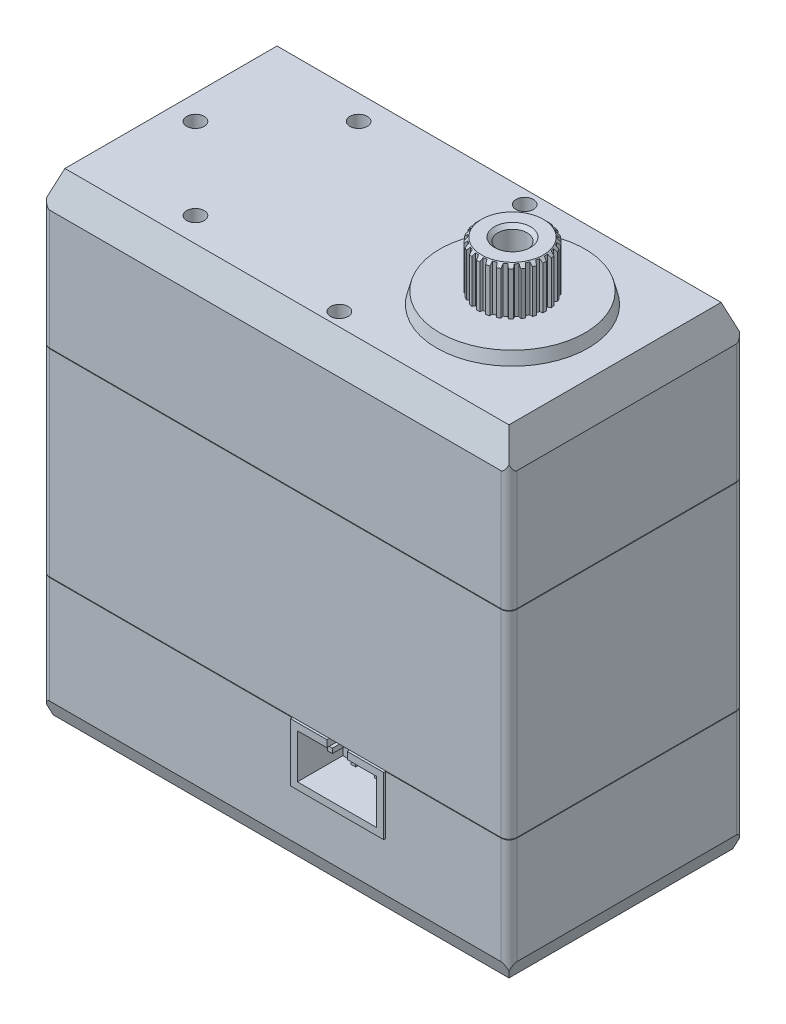
SolidWorks part; units mm, degrees
ref_plane "Front Plane" through (0, 0, 0) normal (0, 0, 1) x (1, 0, 0)
ref_plane "Top Plane" through (0, 0, 0) normal (0, 1, 0) x (1, 0, 0)
ref_plane "Right Plane" through (0, 0, 0) normal (1, 0, 0) x (0, 0, -1)
sketch "Sketch1" plane through (0, 0, 0) normal (0, 1, 0) x (1, 0, 0)
  line L1 (9.8, -10.1) -> (-30.3, -10.1)
  line L2 (9.8, -10.1) -> (9.8, 10.1)
  line L3 (9.8, 10.1) -> (-30.3, 10.1)
  line L4 (-30.3, -10.1) -> (-30.3, 10.1)
  line L5 (9.8, -10.1) -> (-30.3, 10.1) construction
  line L6 (9.8, 10.1) -> (-30.3, -10.1) construction
  point P0 (-10.25, 0)
  dimension "D1" = 20.2
  dimension "D2" = 40.1
  dimension "D3" = 9.8
extrude "Boss-Extrude1" add sketch "Sketch1" along normal blind 40.6
sketch "Sketch2" plane through (0, 0, 0) normal (0, -1, 0) x (1, 0, 0)
  circle A0 centre (0, 0) radius 6.5
  dimension "D1" = 13
extrude "Boss-Extrude2" add sketch "Sketch2" along normal blind 1.5 draft 15
extrude "Boss-Extrude3" add sketch "Sketch2<2>" against normal blind 1 draft 15 from surface starting at face at (-10.25, 40.6, 0)
sketch "Sketch2<2>" plane through (0, 0, 0) normal (0, -1, 0) x (1, 0, 0) same geometry as "Sketch2"
sketch "Sketch3" plane through (0, 41.6, 0) normal (0, 1, 0) x (1, 0, 0)
  circle A0 centre (0, 0) radius 2.95
  dimension "D1" = 5.9
extrude "Boss-Extrude4" add sketch "Sketch3" along normal blind 4
chamfer "Chamfer1" distance 0.3 angle 45 1 edges at (0, 45.6, 2.95)
sketch "Sketch4" plane through (0, 45.6, 0) normal (0, 1, 0) x (1, 0, 0)
  line L0 (-0.2268, 2.9413) -> (-0.144, 2.7138)
  line L1 (-0.144, 2.7138) -> (0.144, 2.7138)
  line L2 (0.144, 2.7138) -> (0.2268, 2.9413)
  line L3 (0, 0) -> (0, 2.95) construction
  line L4 (0.5118, 2.9053) -> (0.5354, 2.6643)
  line L5 (0.5354, 2.6643) -> (0.8144, 2.5927)
  line L6 (0.8144, 2.5927) -> (0.9512, 2.7925)
  line L7 (1.2182, 2.6867) -> (1.1812, 2.4475)
  line L8 (1.1812, 2.4475) -> (1.4336, 2.3087)
  line L9 (1.4336, 2.3087) -> (1.6157, 2.4682)
  line L10 (1.8481, 2.2994) -> (1.7527, 2.0769)
  line L11 (1.7527, 2.0769) -> (1.9627, 1.8797)
  line L12 (1.9627, 1.8797) -> (2.1788, 1.9888)
  line L13 (2.3619, 1.7675) -> (2.2142, 1.5757)
  line L14 (2.2142, 1.5757) -> (2.3685, 1.3325)
  line L15 (2.3685, 1.3325) -> (2.6049, 1.3845)
  line L16 (2.7272, 1.1246) -> (2.5365, 0.9756)
  line L17 (2.5365, 0.9756) -> (2.6255, 0.7016)
  line L18 (2.6255, 0.7016) -> (2.8674, 0.6932)
  line L19 (2.9212, 0.4111) -> (2.6994, 0.3141)
  line L20 (2.6994, 0.3141) -> (2.7175, 0.0267)
  line L21 (2.7175, 0.0267) -> (2.9497, -0.0417)
  line L22 (2.9317, -0.3283) -> (2.6927, -0.367)
  line L23 (2.6927, -0.367) -> (2.6387, -0.65)
  line L24 (2.6387, -0.65) -> (2.8467, -0.7739)
  line L25 (2.7579, -1.0471) -> (2.5168, -1.0252)
  line L26 (2.5168, -1.0252) -> (2.3942, -1.2858)
  line L27 (2.3942, -1.2858) -> (2.5648, -1.4576)
  line L28 (2.4109, -1.7001) -> (2.1828, -1.6189)
  line L29 (2.1828, -1.6189) -> (1.9992, -1.8408)
  line L30 (1.9992, -1.8408) -> (2.1217, -2.0496)
  line L31 (1.9123, -2.2462) -> (1.7116, -2.1108)
  line L32 (1.7116, -2.1108) -> (1.4786, -2.2802)
  line L33 (1.4786, -2.2802) -> (1.5453, -2.5129)
  line L34 (1.2936, -2.6512) -> (1.1329, -2.4702)
  line L35 (1.1329, -2.4702) -> (0.8651, -2.5762)
  line L36 (0.8651, -2.5762) -> (0.8719, -2.8182)
  line L37 (0.5937, -2.8896) -> (0.483, -2.6743)
  line L38 (0.483, -2.6743) -> (0.1972, -2.7104)
  line L39 (0.1972, -2.7104) -> (0.1436, -2.9465)
  line L40 (-0.1436, -2.9465) -> (-0.1972, -2.7104)
  line L41 (-0.1972, -2.7104) -> (-0.483, -2.6743)
  line L42 (-0.483, -2.6743) -> (-0.5937, -2.8896)
  line L43 (-0.8719, -2.8182) -> (-0.8651, -2.5762)
  line L44 (-0.8651, -2.5762) -> (-1.1329, -2.4702)
  line L45 (-1.1329, -2.4702) -> (-1.2936, -2.6512)
  line L46 (-1.5453, -2.5129) -> (-1.4786, -2.2802)
  line L47 (-1.4786, -2.2802) -> (-1.7116, -2.1108)
  line L48 (-1.7116, -2.1108) -> (-1.9123, -2.2462)
  line L49 (-2.1217, -2.0496) -> (-1.9992, -1.8408)
  line L50 (-1.9992, -1.8408) -> (-2.1828, -1.6189)
  line L51 (-2.1828, -1.6189) -> (-2.4109, -1.7001)
  line L52 (-2.5648, -1.4576) -> (-2.3942, -1.2858)
  line L53 (-2.3942, -1.2858) -> (-2.5168, -1.0252)
  line L54 (-2.5168, -1.0252) -> (-2.7579, -1.0471)
  line L55 (-2.8467, -0.7739) -> (-2.6387, -0.65)
  line L56 (-2.6387, -0.65) -> (-2.6927, -0.367)
  line L57 (-2.6927, -0.367) -> (-2.9317, -0.3283)
  line L58 (-2.9497, -0.0417) -> (-2.7175, 0.0267)
  line L59 (-2.7175, 0.0267) -> (-2.6994, 0.3141)
  line L60 (-2.6994, 0.3141) -> (-2.9212, 0.4111)
  line L61 (-2.8674, 0.6932) -> (-2.6255, 0.7016)
  line L62 (-2.6255, 0.7016) -> (-2.5365, 0.9756)
  line L63 (-2.5365, 0.9756) -> (-2.7272, 1.1246)
  line L64 (-2.6049, 1.3845) -> (-2.3685, 1.3325)
  line L65 (-2.3685, 1.3325) -> (-2.2142, 1.5757)
  line L66 (-2.2142, 1.5757) -> (-2.3619, 1.7675)
  line L67 (-2.1788, 1.9888) -> (-1.9627, 1.8797)
  line L68 (-1.9627, 1.8797) -> (-1.7527, 2.0769)
  line L69 (-1.7527, 2.0769) -> (-1.8481, 2.2994)
  line L70 (-1.6157, 2.4682) -> (-1.4336, 2.3087)
  line L71 (-1.4336, 2.3087) -> (-1.1812, 2.4475)
  line L72 (-1.1812, 2.4475) -> (-1.2182, 2.6867)
  line L73 (-0.9512, 2.7925) -> (-0.8144, 2.5927)
  line L74 (-0.8144, 2.5927) -> (-0.5354, 2.6643)
  line L75 (-0.5354, 2.6643) -> (-0.5118, 2.9053)
  circle A0 centre (0, 0) radius 2.95 construction
  arc A1 (0.2268, 2.9413) -> (-0.2268, 2.9413) centre (0, 0) ccw
  arc A2 (0.9512, 2.7925) -> (0.5118, 2.9053) centre (0, 0) ccw
  arc A3 (1.6157, 2.4682) -> (1.2182, 2.6867) centre (0, 0) ccw
  arc A4 (2.1788, 1.9888) -> (1.8481, 2.2994) centre (0, 0) ccw
  arc A5 (2.6049, 1.3845) -> (2.3619, 1.7675) centre (0, 0) ccw
  arc A6 (2.8674, 0.6932) -> (2.7272, 1.1246) centre (0, 0) ccw
  arc A7 (2.9497, -0.0417) -> (2.9212, 0.4111) centre (0, 0) ccw
  arc A8 (2.8467, -0.7739) -> (2.9317, -0.3283) centre (0, 0) ccw
  arc A9 (2.5648, -1.4576) -> (2.7579, -1.0471) centre (0, 0) ccw
  arc A10 (2.1217, -2.0496) -> (2.4109, -1.7001) centre (0, 0) ccw
  arc A11 (1.5453, -2.5129) -> (1.9123, -2.2462) centre (0, 0) ccw
  arc A12 (0.8719, -2.8182) -> (1.2936, -2.6512) centre (0, 0) ccw
  arc A13 (0.1436, -2.9465) -> (0.5937, -2.8896) centre (0, 0) ccw
  arc A14 (-0.5937, -2.8896) -> (-0.1436, -2.9465) centre (0, 0) ccw
  arc A15 (-1.2936, -2.6512) -> (-0.8719, -2.8182) centre (0, 0) ccw
  arc A16 (-1.9123, -2.2462) -> (-1.5453, -2.5129) centre (0, 0) ccw
  arc A17 (-2.4109, -1.7001) -> (-2.1217, -2.0496) centre (0, 0) ccw
  arc A18 (-2.7579, -1.0471) -> (-2.5648, -1.4576) centre (0, 0) ccw
  arc A19 (-2.9317, -0.3283) -> (-2.8467, -0.7739) centre (0, 0) ccw
  arc A20 (-2.9212, 0.4111) -> (-2.9497, -0.0417) centre (0, 0) ccw
  arc A21 (-2.7272, 1.1246) -> (-2.8674, 0.6932) centre (0, 0) ccw
  arc A22 (-2.3619, 1.7675) -> (-2.6049, 1.3845) centre (0, 0) ccw
  arc A23 (-1.8481, 2.2994) -> (-2.1788, 1.9888) centre (0, 0) ccw
  arc A24 (-1.2182, 2.6867) -> (-1.6157, 2.4682) centre (0, 0) ccw
  arc A25 (-0.5118, 2.9053) -> (-0.9512, 2.7925) centre (0, 0) ccw
  point P4 (0, 2.7138)
  point P106 (0, 0)
  dimension "D1" = 110
  dimension "D4" = 25
extrude "Cut-Extrude1" cut sketch "Sketch4" against normal up to surface (4 mm away) up to face at (0, 41.6, 2.95)
sketch "Sketch5" plane through (0, 45.6, 0) normal (0, 1, 0) x (1, 0, 0)
  circle A0 centre (0, 0) radius 1.25
  dimension "D1" = 2.5
extrude "Cut-Extrude2" cut sketch "Sketch5" against normal blind 5
chamfer "Chamfer2" distance 0.3 angle 45 1 edges at (0, 45.6, 1.25)
sketch "Sketch6" plane through (0, -1.5, 0) normal (0, -1, 0) x (1, 0, 0)
  circle A0 centre (0, 0) radius 3
  circle A1 centre (0, 0) radius 1.2
  dimension "D1" = 6
  dimension "D2" = 2.4
extrude "Boss-Extrude5" add sketch "Sketch6" along normal blind 4.4
chamfer "Chamfer3" distance 0.3 angle 45 1 edges at (0, -5.9, -3)
sketch "Sketch7" plane through (0, 40.6, 0) normal (0, 1, 0) x (1, 0, 0)
  line L0 (-20.2, 7) -> (-20.2, -7) construction
  line L1 (-6.9, 7.95) -> (-6.9, -7.95) construction
  line L2 (0, 0) -> (-27.2, 0) construction
  line L3 (-30.3, 10.1) -> (-30.3, -10.1) construction
  circle A0 centre (-20.2, 7) radius 0.75
  circle A1 centre (-6.9, 7.95) radius 0.75
  circle A2 centre (-6.9, -7.95) radius 0.75
  circle A3 centre (-20.2, -7) radius 0.75
  circle A4 centre (-27.2, 0) radius 0.75
  point P7 (-20.2, 0)
  point P8 (-6.9, 0)
  dimension "D6" = 1.5
  dimension "D1" = 14
  dimension "D2" = 15.9
  dimension "D3" = 7
  dimension "D4" = 3.1
  dimension "D5" = 13.3
extrude "Cut-Extrude3" cut sketch "Sketch7" against normal blind 5
sketch "Sketch8" plane through (0, 0, 0) normal (0, -1, 0) x (1, 0, 0)
  line L0 (9.8, -10.1) -> (-30.3, -10.1) construction
  line L1 (-27.85, 7.6) -> (7.35, 7.6) construction
  line L2 (-27.85, 7.6) -> (-27.85, -7.6) construction
  line L3 (-27.85, -7.6) -> (7.35, -7.6) construction
  line L4 (7.35, 7.6) -> (7.35, -7.6) construction
  line L5 (-30.3, -10.1) -> (-30.3, 10.1) construction
  line L6 (-12.75, 7.6) -> (-12.75, -7.6) construction
  circle A0 centre (-27.85, 7.6) radius 0.75
  circle A1 centre (-12.75, 7.6) radius 0.75
  circle A2 centre (7.35, 7.6) radius 0.75
  circle A3 centre (7.35, -7.6) radius 0.75
  circle A4 centre (-12.75, -7.6) radius 0.75
  circle A5 centre (-27.85, -7.6) radius 0.75
  point P6 (-10.25, -10.1)
  point P7 (-10.25, -7.6)
  point P10 (-30.3, 0)
  point P11 (-27.85, 0)
  dimension "D4" = 1.5
  dimension "D1" = 15.2
  dimension "D2" = 35.2
  dimension "D3" = 15.1
extrude "Cut-Extrude4" cut sketch "Sketch8" against normal blind 5
sketch "Sketch9" plane through (0, 40.6, 0) normal (0, 1, 0) x (1, 0, 0)
  line L0 (-30.25, 10.05) -> (-30.25, -10.05)
  line L1 (-30.25, -10.05) -> (9.75, -10.05)
  line L2 (9.75, -10.05) -> (9.75, 10.05)
  line L3 (9.75, 10.05) -> (-30.25, 10.05)
  line L4 (-30.3, 10.1) -> (-30.3, -10.1)
  line L5 (-30.3, -10.1) -> (9.8, -10.1)
  line L6 (9.8, -10.1) -> (9.8, 10.1)
  line L7 (9.8, 10.1) -> (-30.3, 10.1)
  line L8 (-30.3, 10.1) -> (-30.3, -10.1)
  line L9 (-30.3, -10.1) -> (9.8, -10.1)
  line L10 (9.8, -10.1) -> (9.8, 10.1)
  line L11 (9.8, 10.1) -> (-30.3, 10.1)
  dimension "D1" = 0
  dimension "D2" = 0.05
extrude "Cut-Extrude5" cut sketch "Sketch9" against normal blind 0.05 from offset 13 offset against normal yes
extrude "Cut-Extrude6" cut sketch "Sketch9<2>" against normal blind 0.05 from offset 30 offset against normal yes
sketch "Sketch9<2>" plane through (0, 40.6, 0) normal (0, 1, 0) x (1, 0, 0) same geometry as "Sketch9"
chamfer "Chamfer4" distance 1 angle 70 4 edges at (9.8, 40.6, 0) (-10.25, 40.6, -10.1) (-30.3, 40.6, 0) (-10.25, 40.6, 10.1) first distance on face at (-27.2, 40.6, 0.75)
chamfer "Chamfer5" distance 0.5 angle 70 4 edges at (-10.25, 0, 10.1) (9.8, 0, 0) (-10.25, 0, -10.1) (-30.3, 0, 0) first distance on face at (-27.85, 0, -8.35)
sketch "Sketch10" plane through (0, 0, 10.1) normal (0, 0, 1) x (1, 0, 0)
  line L0 (-30.3, 10.55) -> (9.8, 10.55) construction
  line L1 (-8.8, 10.55) -> (-0.8, 10.55)
  line L2 (-8.8, 10.55) -> (-8.8, 5.55)
  line L3 (-8.8, 5.55) -> (-0.8, 5.55)
  line L4 (-0.8, 10.55) -> (-0.8, 5.55)
  line L5 (-30.3, 10.55) -> (-30.3, 1.3737) construction
  line L6 (-8.2, 9.95) -> (-8.2, 6.15)
  line L7 (-8.2, 6.15) -> (-1.4, 6.15)
  line L8 (-1.4, 9.95) -> (-1.4, 6.15)
  line L9 (-8.2, 9.95) -> (-1.4, 9.95)
  dimension "D1" = 8
  dimension "D2" = 5
  dimension "D3" = 21.5
  dimension "D4" = 0.6
extrude "Boss-Extrude6" add sketch "Sketch10" along normal blind 0.15
sketch "Sketch11" plane through (0, 0, 10.1) normal (0, 0, 1) x (1, 0, 0)
  line L4 (-1.4, 6.15) -> (-1.4, 9.95)
  line L5 (-1.4, 9.95) -> (-8.2, 9.95)
  line L6 (-8.2, 9.95) -> (-8.2, 6.15)
  line L7 (-8.2, 6.15) -> (-1.4, 6.15)
  line L8 (-1.4, 6.15) -> (-1.4, 9.95)
  line L9 (-1.4, 9.95) -> (-8.2, 9.95)
  line L10 (-8.2, 9.95) -> (-8.2, 6.15)
  line L11 (-8.2, 6.15) -> (-1.4, 6.15)
  dimension "D1" = 0
extrude "Cut-Extrude7" cut sketch "Sketch11" against normal blind 3.75
sketch "Sketch12" plane through (0, 0, 10.25) normal (0, 0, 1) x (1, 0, 0)
  line L0 (-1.4, 9.95) -> (-8.2, 9.95) construction
  line L1 (-5.675, 9.95) -> (-3.925, 9.95)
  line L2 (-5.675, 9.95) -> (-5.675, 10.55)
  line L3 (-5.675, 10.55) -> (-3.925, 10.55)
  line L4 (-3.925, 9.95) -> (-3.925, 10.55)
  line L5 (-0.8, 10.55) -> (-8.8, 10.55) construction
  line L6 (-8.8, 5.55) -> (-0.8, 5.55) construction
  point P10 (-4.8, 5.55)
  point P11 (-4.8, 9.95)
  dimension "D1" = 1.75
extrude "Cut-Extrude8" cut sketch "Sketch12" against normal up to surface (3.9 mm away) up to face at (-4.8, 8.05, 6.35)
sketch "Sketch13" plane through (0, 0, 6.35) normal (0, 0, 1) x (1, 0, 0)
  line L0 (-6.8, 8.55) -> (-2.8, 8.55) construction
  line L1 (-8.2, 6.15) -> (-1.4, 6.15) construction
  line L2 (-6.6, 8.35) -> (-7, 8.35)
  line L3 (-6.6, 8.35) -> (-6.6, 8.75)
  line L4 (-6.6, 8.75) -> (-7, 8.75)
  line L5 (-7, 8.35) -> (-7, 8.75)
  line L6 (-6.6, 8.35) -> (-7, 8.75) construction
  line L7 (-6.6, 8.75) -> (-7, 8.35) construction
  line L8 (-4.6, 8.35) -> (-5, 8.35)
  line L9 (-4.6, 8.35) -> (-4.6, 8.75)
  line L10 (-4.6, 8.75) -> (-5, 8.75)
  line L11 (-5, 8.35) -> (-5, 8.75)
  line L12 (-4.6, 8.35) -> (-5, 8.75) construction
  line L13 (-4.6, 8.75) -> (-5, 8.35) construction
  line L14 (-2.6, 8.35) -> (-3, 8.35)
  line L15 (-2.6, 8.35) -> (-2.6, 8.75)
  line L16 (-2.6, 8.75) -> (-3, 8.75)
  line L17 (-3, 8.35) -> (-3, 8.75)
  line L18 (-2.6, 8.35) -> (-3, 8.75) construction
  line L19 (-2.6, 8.75) -> (-3, 8.35) construction
  line L20 (-1.4, 9.95) -> (-3.925, 9.95) construction
  point P6 (-4.8, 8.55)
  point P17 (-4.8, 6.15)
  dimension "D1" = 0.4
  dimension "D2" = 4
  dimension "D3" = 1.4
extrude "Boss-Extrude7" add sketch "Sketch13" along normal blind 2.5
mirror "Mirror1" about plane through (0, 0, 0) normal (0, 0, 1) of "Boss-Extrude7", "Cut-Extrude8", "Cut-Extrude7", "Boss-Extrude6"
fillet "Fillet1" radius 0.7 12 edges at (9.75, 27.575, -10.05) (9.8, 19.075, -10.1) (9.75, 10.575, -10.05) (9.75, 10.575, 10.05) (9.75, 27.575, 10.05) (9.8, 19.075, 10.1) (-30.25, 10.575, 10.05) (-30.25, 27.575, 10.05) (-30.3, 19.075, 10.1) (-30.25, 27.575, -10.05) (-30.25, 10.575, -10.05) (-30.3, 19.075, -10.1)
fillet "Fillet2" radius 0.7 8 edges at (9.8, 5.9619, -10.1) (9.8, 5.9619, 10.1) (-30.3, 5.9619, 10.1) (-30.3, 5.9619, -10.1) (-30.3, 32.7263, -10.1) (-30.3, 32.7263, 10.1) (9.8, 32.7263, -10.1) (9.8, 32.7263, 10.1)
sketch "Sketch15" plane through (0, -1.5, 0) normal (0, -1, 0) x (1, 0, 0)
  circle A0 centre (0, 0) radius 3.5
  circle A1 centre (0, 0) radius 3 construction
  circle A2 centre (0, 0) radius 3
  dimension "D1" = 7
extrude "Boss-Extrude8" add sketch "Sketch15" along normal blind 0.15
